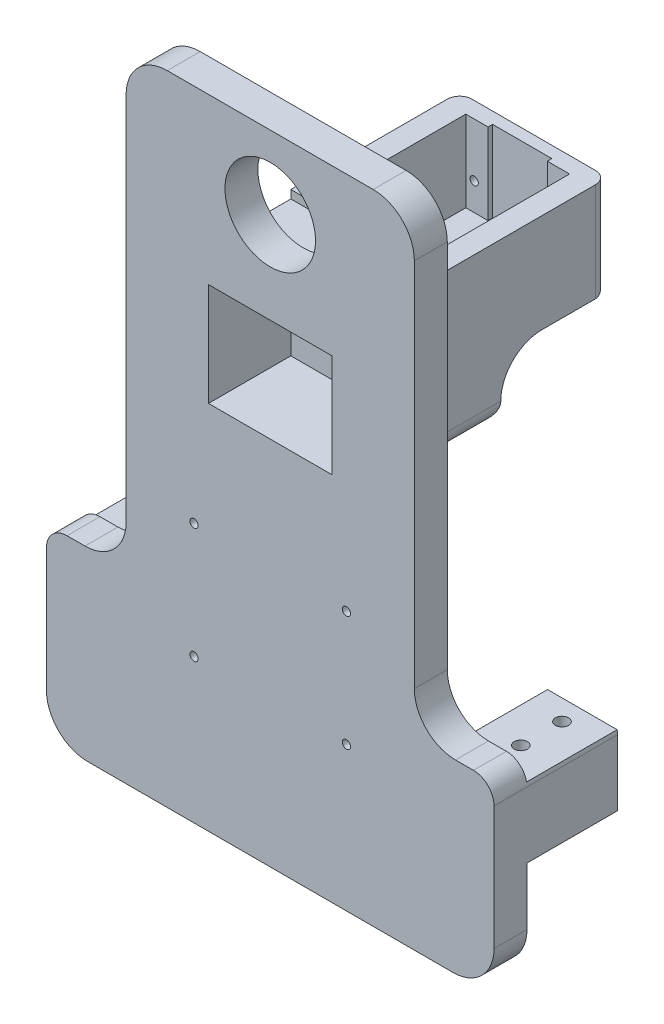
SolidWorks part; units mm, degrees
ref_plane "前视基准面" through (0, 0, 0) normal (0, 0, 1) x (1, 0, 0)
ref_plane "上视基准面" through (0, 0, 0) normal (0, 1, 0) x (1, 0, 0)
ref_plane "右视基准面" through (0, 0, 0) normal (1, 0, 0) x (0, 0, -1)
other "Configuration Table"
sketch "草图3" plane through (0, 0, 0) normal (0, 1, 0) x (1, 0, 0)
  line L1 (-18, -25) -> (18, -25)
  line L2 (-18, -25) -> (-18, 25)
  line L3 (-18, 25) -> (18, 25)
  line L4 (18, -25) -> (18, 25)
  line L5 (-18, -25) -> (18, 25) construction
  line L6 (-18, 25) -> (18, -25) construction
  point P0 (0, 0)
  dimension "D1" = 36
  dimension "D2" = 50
extrude "凸台-拉伸1" add sketch "草图3" along normal blind 24
sketch "草图4" plane through (0, 24, 0) normal (0, 1, 0) x (1, 0, 0)
  line L1 (-12.4, -15.9) -> (12.4, -15.9)
  line L2 (-12.4, -15.9) -> (-12.4, 15.9)
  line L3 (-12.4, 15.9) -> (12.4, 15.9)
  line L4 (12.4, -15.9) -> (12.4, 15.9)
  line L5 (-12.4, -15.9) -> (12.4, 15.9) construction
  line L6 (-12.4, 15.9) -> (12.4, -15.9) construction
  point P0 (0, 0)
  dimension "D1" = 24.8
  dimension "D2" = 31.8
extrude "切除-拉伸1" cut sketch "草图4" against normal blind 19.7
sketch "草图5" plane through (0, 24, 0) normal (0, 1, 0) x (1, 0, 0)
  line L0 (12.4, 15.9) -> (-12.4, 15.9) construction
  line L1 (-7, 14.8) -> (7, 14.8)
  line L2 (-7, 14.8) -> (-7, 17)
  line L3 (-7, 17) -> (7, 17)
  line L4 (7, 14.8) -> (7, 17)
  line L5 (-7, 14.8) -> (7, 17) construction
  line L6 (-7, 17) -> (7, 14.8) construction
  point P0 (0, 15.9)
  dimension "D1" = 14
  dimension "D2" = 2.2
extrude "切除-拉伸3" cut sketch "草图5" against normal blind 19.7 contours L3 L4 L1 L2
sketch "草图6" plane through (0, 24, 0) normal (0, 1, 0) x (1, 0, 0)
  line L0 (-12.4, -15.9) -> (12.4, -15.9) construction
  line L1 (-9.25, -17.8) -> (9.25, -17.8)
  line L2 (-9.25, -17.8) -> (-9.25, -14)
  line L3 (-9.25, -14) -> (9.25, -14)
  line L4 (9.25, -17.8) -> (9.25, -14)
  line L5 (-9.25, -17.8) -> (9.25, -14) construction
  line L6 (-9.25, -14) -> (9.25, -17.8) construction
  point P0 (0, -15.9)
  dimension "D1" = 18.5
  dimension "D2" = 3.8
extrude "切除-拉伸4" cut sketch "草图6" against normal blind 14.7
sketch "草图7" plane through (0, 24, 0) normal (0, 1, 0) x (1, 0, 0)
  line L0 (-18, -25) -> (18, -25) construction
  line L1 (-12.4, -37.1402) -> (12.4, -37.1402)
  line L2 (-12.4, -37.1402) -> (-12.4, -12.8598)
  line L3 (-12.4, -12.8598) -> (12.4, -12.8598)
  line L4 (12.4, -37.1402) -> (12.4, -12.8598)
  line L5 (-12.4, -37.1402) -> (12.4, -12.8598) construction
  line L6 (-12.4, -12.8598) -> (12.4, -37.1402) construction
  point P0 (0, -25)
  dimension "D1" = 24.8
extrude "切除-拉伸5" cut sketch "草图7" against normal blind 2
sketch "草图8" plane through (0, 0, 25) normal (0, 0, 1) x (1, 0, 0)
  line L0 (18, 24) -> (18, 0) construction
  line L1 (-18, 0) -> (18, 0) construction
  line L2 (-18, 24) -> (-18, 0) construction
  circle A0 centre (10.65, 7.2) radius 2
  circle A1 centre (-10.65, 7.2) radius 2
  dimension "D1" = 7.35
  dimension "D3" = 7.35
  dimension "D2" = 7.2
  dimension "D4" = 7.2
extrude "切除-拉伸6" cut sketch "草图8" against normal blind 6.4
sketch "草图9" plane through (0, 0, 18.6) normal (0, 0, 1) x (1, 0, 0)
  circle A0 centre (10.65, 7.2) radius 1
  circle A1 centre (-10.65, 7.2) radius 1
extrude "切除-拉伸7" cut sketch "草图9" against normal blind 6.4
sketch "草图10" plane through (0, 0, -25) normal (0, 0, -1) x (-1, 0, 0)
  line L0 (-18, 24) -> (-18, 0) construction
  line L1 (-18, 0) -> (18, 0) construction
  line L2 (18, 24) -> (18, 0) construction
  circle A0 centre (-10.565, 11) radius 2
  circle A1 centre (10.56, 11) radius 2
  dimension "D1" = 7.435
  dimension "D3" = 7.44
  dimension "D2" = 11
  dimension "D4" = 11
extrude "切除-拉伸8" cut sketch "草图10" against normal blind 7.4
sketch "草图11" plane through (0, 0, -17.6) normal (0, 0, -1) x (-1, 0, 0)
  circle A0 centre (10.56, 11) radius 1
  circle A1 centre (-10.565, 11) radius 1
extrude "切除-拉伸9" cut sketch "草图11" against normal blind 7.4
sketch "草图14" plane through (0, 0, 25) normal (0, 0, 1) x (1, 0, 0)
  line L1 (-26.5003, 33.3651) -> (21.1929, 33.3651)
  line L2 (-26.5003, 33.3651) -> (-26.5003, -8.5784)
  line L3 (-26.5003, -8.5784) -> (21.1929, -8.5784)
  line L4 (21.1929, 33.3651) -> (21.1929, -8.5784)
extrude "切除-拉伸12" cut sketch "草图14" against normal blind 4
sketch "草图16" plane through (0, 0, -25) normal (0, 0, -1) x (-1, 0, 0)
  line L1 (-33.7246, 32.2994) -> (35.4423, 32.2994)
  line L2 (-33.7246, 32.2994) -> (-33.7246, -7.1228)
  line L3 (-33.7246, -7.1228) -> (35.4423, -7.1228)
  line L4 (35.4423, 32.2994) -> (35.4423, -7.1228)
extrude "切除-拉伸13" cut sketch "草图16" against normal blind 5
sketch "草图18" plane through (0, 24, 0) normal (0, 1, 0) x (1, 0, 0)
  line L113 (-12.6, -16.1) -> (12.6, -16.1)
  line L114 (-12.6, 16.1) -> (-12.6, -16.1)
  line L115 (-7.2, 16.1) -> (-12.6, 16.1)
  line L116 (-7.2, 17.2) -> (-7.2, 16.1)
  line L117 (7.2, 17.2) -> (-7.2, 17.2)
  line L118 (7.2, 16.1) -> (7.2, 17.2)
  line L119 (12.6, 16.1) -> (7.2, 16.1)
  line L120 (12.6, -16.1) -> (12.6, 16.1)
  line L121 (-12.6, -16.1) -> (12.6, -16.1)
  line L122 (-12.6, 16.1) -> (-12.6, -16.1)
  line L123 (-7.2, 16.1) -> (-12.6, 16.1)
  line L124 (-7.2, 17.2) -> (-7.2, 16.1)
  line L125 (7.2, 17.2) -> (-7.2, 17.2)
  line L126 (7.2, 16.1) -> (7.2, 17.2)
  line L127 (12.6, 16.1) -> (7.2, 16.1)
  line L128 (12.6, -16.1) -> (12.6, 16.1)
  dimension "D1" = 0.2
extrude "切除-拉伸17" cut sketch "草图18" against normal blind 19.7
sketch "草图19" plane through (0, 22, 0) normal (0, 1, 0) x (1, 0, 0)
  line L14 (9.45, -18) -> (9.45, -15.9)
  line L15 (-9.45, -15.9) -> (-9.45, -18)
  line L16 (-9.45, -18) -> (9.45, -18)
  line L17 (9.45, -15.9) -> (-9.45, -15.9)
  line L18 (9.45, -18) -> (9.45, -15.9)
  line L19 (-9.45, -15.9) -> (-9.45, -18)
  line L20 (-9.45, -18) -> (9.45, -18)
  line L21 (9.45, -15.9) -> (-9.45, -15.9)
  dimension "D1" = 0.2
extrude "切除-拉伸18" cut sketch "草图19" against normal blind 12.7
sketch "草图20" plane through (0, 0, 0) normal (0, -1, 0) x (1, 0, 0)
  line L0 (-18, -20) -> (-18, 21) construction
  line L1 (-18, 6) -> (18, 6)
  line L2 (-18, 6) -> (-18, 36)
  line L3 (-18, 36) -> (18, 36)
  line L4 (18, 6) -> (18, 36)
  line L5 (18, 21) -> (18, -20) construction
  line L6 (18, 21) -> (-18, 21) construction
  dimension "D1" = 30
  dimension "D2" = 15
extrude "凸台-拉伸2" add sketch "草图20" along normal blind 15
sketch "草图22" plane through (0, 0, 36) normal (0, 0, 1) x (1, 0, 0)
  line L0 (0, 0) -> (0, -13) construction
  line L1 (-35, -78) -> (35, -78)
  line L2 (-35, -78) -> (-35, 52)
  line L3 (-35, 52) -> (35, 52)
  line L4 (35, -78) -> (35, 52)
  line L5 (-35, -78) -> (35, 52) construction
  line L6 (-35, 52) -> (35, -78) construction
  point P0 (0, -13)
  dimension "D1" = 70
  dimension "D2" = 130
  dimension "D3" = 13
extrude "凸台-拉伸3" add sketch "草图22" along normal blind 8
sketch "草图25" plane through (0, 0, 0) normal (0, 1, 0) x (1, 0, 0)
  line L1 (-18, -21) -> (18, -21)
  line L2 (-18, -21) -> (-18, -36)
  line L3 (-18, -36) -> (18, -36)
  line L4 (18, -21) -> (18, -36)
sketch "草图26" plane through (0, 0, 44) normal (0, 0, 1) x (1, 0, 0)
  line L0 (-12.6, 4.3) -> (12.6, 4.3) construction
  line L4 (35, -78) -> (35, 52)
  line L5 (35, 52) -> (-35, 52)
  line L6 (-35, 52) -> (-35, -78)
  line L7 (-35, -78) -> (35, -78)
  line L8 (35, -78) -> (35, 52)
  line L9 (35, 52) -> (-35, 52)
  line L10 (-35, 52) -> (-35, -78)
  line L11 (-35, -78) -> (35, -78)
  circle A0 centre (10.65, 7.2) radius 2 construction
  circle A1 centre (10.65, 7.2) radius 2
  circle A2 centre (-10.65, 7.2) radius 2 construction
  circle A3 centre (-10.65, 7.2) radius 2
  circle A4 centre (0, 39.208) radius 11
  dimension "D2" = 34.908
  dimension "D1" = 0
extrude "凸台-拉伸5" add sketch "草图25" along normal up to surface (22 mm away) up to face at (0, 22, 17.8)
extrude "切除-拉伸21" cut sketch "草图26" against normal blind 23 flip side to cut
sketch "草图27" plane through (0, 0, 36) normal (0, 0, -1) x (-1, 0, 0)
  line L0 (-51.906, -59.45) -> (-39.806, -59.45)
  line L1 (-54.356, -57) -> (-37.356, -57)
  line L2 (-54.356, -57) -> (-54.356, -74)
  line L3 (-54.356, -74) -> (-37.356, -74)
  line L4 (-37.356, -57) -> (-37.356, -74)
  line L5 (-39.806, -59.45) -> (-39.806, -71.55)
  line L6 (-51.906, -71.55) -> (-39.806, -71.55)
  line L7 (-51.906, -59.45) -> (-51.906, -71.55)
  line L8 (-18, -15) -> (18, -15) construction
  line L9 (0, -18.8076) -> (0, -69.0561) construction
  dimension "D1" = 17
  dimension "D2" = 17
  dimension "D4" = 42
  dimension "D5" = 37.356
  dimension "D3" = 2.45
sketch "草图28" plane through (35, 0, 0) normal (1, 0, 0) x (0, 0, -1)
  line L0 (-44, -78) -> (-44, 52) construction
  line L2 (-44, -53) -> (-36, -53)
  line L3 (-44, -53) -> (-44, -78)
  line L4 (-44, -78) -> (-36, -78)
  line L5 (-36, -53) -> (-36, -78)
  dimension "D1" = 4
extrude "凸台-拉伸6" add sketch "草图28" along normal up to vertex (19.356 mm away) contours L2 L5 L4 L3 up to point (54.356, -57, 36)
extrude "凸台-拉伸7" add sketch "草图27" along normal blind 22
mirror "镜向1" about plane through (0, 0, 0) normal (1, 0, 0) of "凸台-拉伸7", "凸台-拉伸6"
sketch "草图29" plane through (0, 52, 0) normal (0, 1, 0) x (1, 0, 0)
  line L1 (-35, -36) -> (35, -36)
  line L2 (-35, -36) -> (-35, -44)
  line L3 (-35, -44) -> (35, -44)
  line L4 (35, -36) -> (35, -44)
extrude "凸台-拉伸8" add sketch "草图29" along normal blind 5
sketch "草图30" plane through (0, -74, 0) normal (0, -1, 0) x (1, 0, 0)
  line L0 (-54.356, 36) -> (54.356, 36) construction
  circle A0 centre (45.856, 29) radius 1.6
  circle A1 centre (45.856, 19) radius 1.6
  dimension "D1" = 7
  dimension "D2" = 10
extrude "切除-拉伸22" cut sketch "草图30" against normal blind 45
mirror "镜向2" about plane through (0, 0, 0) normal (1, 0, 0) of "切除-拉伸22"
sketch "草图31" plane through (0, 0, 36) normal (0, 0, -1) x (-1, 0, 0)
  line L0 (0, 13.2) -> (0, -13.2) construction
  line L5 (-25, -48.9797) -> (25, -48.9797) construction
  circle A0 centre (-18.5, -34.9797) radius 2.5
  circle A5 centre (18.5, -34.9797) radius 2.5
  circle A6 centre (18.5, -62.9797) radius 2.5
  circle A7 centre (-18.5, -62.9797) radius 2.5
  point P0 (0, -48.9797)
  dimension "D3" = 18.5
  dimension "D4" = 14
  dimension "D5" = 2
  dimension "D6" = 2
fillet "圆角2" radius 10 2 edges at (-35, -53, 40) (35, -53, 40)
fillet "圆角3" radius 5 2 edges at (-54.356, -53, 40) (54.356, -53, 40)
fillet "圆角4" radius 10 1 edges at (0, 0, 6)
extrude "凸台-拉伸9" add sketch "草图31" along normal blind 5
sketch "草图34" plane through (0, 0, 31) normal (0, 0, -1) x (-1, 0, 0)
  circle A0 centre (-18.5, -62.9797) radius 1
  circle A1 centre (18.5, -62.9797) radius 1
  circle A2 centre (18.5, -34.9797) radius 1
  circle A3 centre (-18.5, -34.9797) radius 1
extrude "切除-拉伸27" cut sketch "草图34" against normal blind 31
sketch "草图35" plane through (0, 24, 0) normal (0, 1, 0) x (1, 0, 0)
  line L1 (-12.6, 16.1) -> (12.6, 16.1)
  line L2 (-12.6, 16.1) -> (-12.6, -21.7224)
  line L3 (-12.6, -21.7224) -> (12.6, -21.7224)
  line L4 (12.6, 16.1) -> (12.6, -21.7224)
extrude "切除-拉伸28" cut sketch "草图35" against normal up to surface (2 mm away) up to face at (0, 22, 21.3667)
fillet "圆角5" radius 5 7 edges at (18, 3.5, 36) (0, 22, 36) (-18, 3.5, 36) (18, -15, 21) (0, -15, 36) (-18, -15, 21) (0, -15, 6)
fillet "圆角6" radius 3 3 edges at (-18, 12, -20) (0, 0, -20) (18, 12, -20)
sketch "草图36" plane through (0, 0, 44) normal (0, 0, 1) x (1, 0, 0)
  line L0 (0, -35.2) -> (0, 35.2) construction
  line L1 (-15, 17) -> (15, 17)
  line L2 (-15, 17) -> (-15, -8)
  line L3 (-15, -8) -> (15, -8)
  line L4 (15, 17) -> (15, -8)
  line L5 (-18, 22) -> (18, 22) construction
  dimension "D1" = 30
  dimension "D2" = 15
  dimension "D3" = 25
  dimension "D4" = 5
extrude "切除-拉伸29" cut sketch "草图36" against normal blind 20
sketch "草图37" plane through (0, -78, 0) normal (0, -1, 0) x (1, 0, 0)
  line L4 (-54.356, 36) -> (54.356, 36)
  line L5 (54.356, 36) -> (54.356, 44)
  line L6 (54.356, 44) -> (-54.356, 44)
  line L7 (-54.356, 44) -> (-54.356, 36)
  line L8 (-54.356, 36) -> (54.356, 36)
  line L9 (54.356, 36) -> (54.356, 44)
  line L10 (54.356, 44) -> (-54.356, 44)
  line L11 (-54.356, 44) -> (-54.356, 36)
  dimension "D1" = 0
extrude "凸台-拉伸10" add sketch "草图37" along normal blind 20
fillet "圆角7" radius 10 4 edges at (-54.356, -98, 40) (54.356, -98, 40) (35, 57, 40) (-35, 57, 40)
